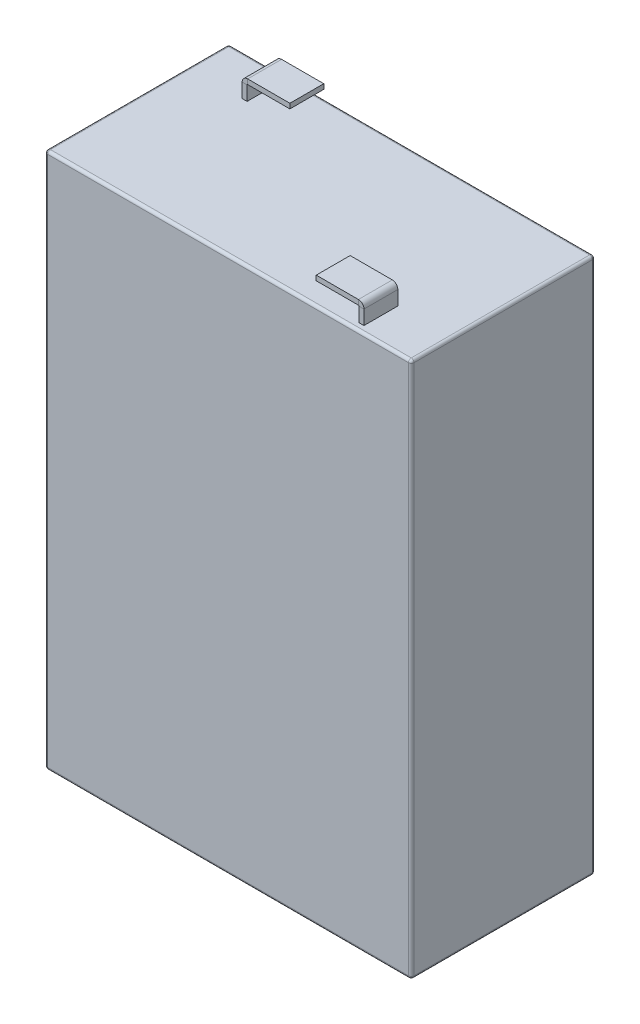
SolidWorks part; units mm, degrees
material "ABS"
ref_plane "Front Plane" through (0, 0, 0) normal (0, 0, 1) x (1, 0, 0)
ref_plane "Top Plane" through (0, 0, 0) normal (0, 1, 0) x (1, 0, 0)
ref_plane "Right Plane" through (0, 0, 0) normal (1, 0, 0) x (0, 0, -1)
sketch "Sketch2" plane through (0, 0, 0) normal (0, 1, 0) x (1, 0, 0)
  line L1 (-33.0848, -16.5989) -> (33.0848, -16.5989)
  line L2 (-33.0848, -16.5989) -> (-33.0848, 16.5989)
  line L3 (-33.0848, 16.5989) -> (33.0848, 16.5989)
  line L4 (33.0848, -16.5989) -> (33.0848, 16.5989)
  line L5 (-33.0848, -16.5989) -> (33.0848, 16.5989) construction
  line L6 (-33.0848, 16.5989) -> (33.0848, -16.5989) construction
  point P0 (0, 0)
  dimension "D1" = 66.1695
  dimension "D2" = 33.1978
extrude "Boss-Extrude1" add sketch "Sketch2" along normal blind 96.901
fillet "Fillet1" radius 0.5 12 edges at (33.0848, 48.4505, 16.5989) (-33.0848, 48.4505, 16.5989) (-33.0848, 0, 0) (0, 0, 16.5989) (33.0848, 0, 0) (33.0848, 48.4505, -16.5989) (-33.0848, 48.4505, -16.5989) (0, 0, -16.5989) (0, 96.901, 16.5989) (-33.0848, 96.901, 0) (0, 96.901, -16.5989) (33.0848, 96.901, 0)
sketch "Sketch3" plane through (0, 96.901, 0) normal (0, 1, 0) x (1, 0, 0)
  line L1 (-23.255, 15.3139) -> (-22.366, 15.3139)
  line L2 (-23.255, 15.3139) -> (-23.255, 9.1925)
  line L3 (-23.255, 9.1925) -> (-22.366, 9.1925)
  line L4 (-22.366, 15.3139) -> (-22.366, 9.1925)
  line L5 (-33.0848, -16.0989) -> (-33.0848, 16.0989) construction
  line L6 (-32.5848, 16.5989) -> (32.5848, 16.5989) construction
  point P8 (0, 0)
  dimension "D1" = 0.889
  dimension "D2" = 6.1214
  dimension "D3" = 9.8298
  dimension "D4" = 1.285
sketch "Sketch4" plane through (0, 0, -16.5989) normal (0, 0, -1) x (-1, 0, 0)
  line L0 (23.255, 96.901) -> (23.255, 99.4824)
  line L1 (23.255, 96.901) -> (22.366, 96.901) construction
  line L2 (22.255, 100.4824) -> (14.635, 100.4824)
  line L3 (-32.5848, 96.901) -> (32.5848, 96.901) construction
  arc A0 (23.255, 99.4824) -> (22.255, 100.4824) centre (22.255, 99.4824) ccw
  point P9 (0, 0)
  point P11 (0, 0)
  dimension "D1" = 1
  dimension "D2" = 7.62
  dimension "D3" = 3.5814
sweep "Sweep1" add profiles "Sketch3" path "Sketch4"
ref_axis "Axis1" through (0, -5.0241, 0) along (0, 1, 0)
pattern_circular "CirPattern1" count 2 every 180 about axis through (0, -5.0241, 0) along (0, 1, 0) of "Sweep1"
